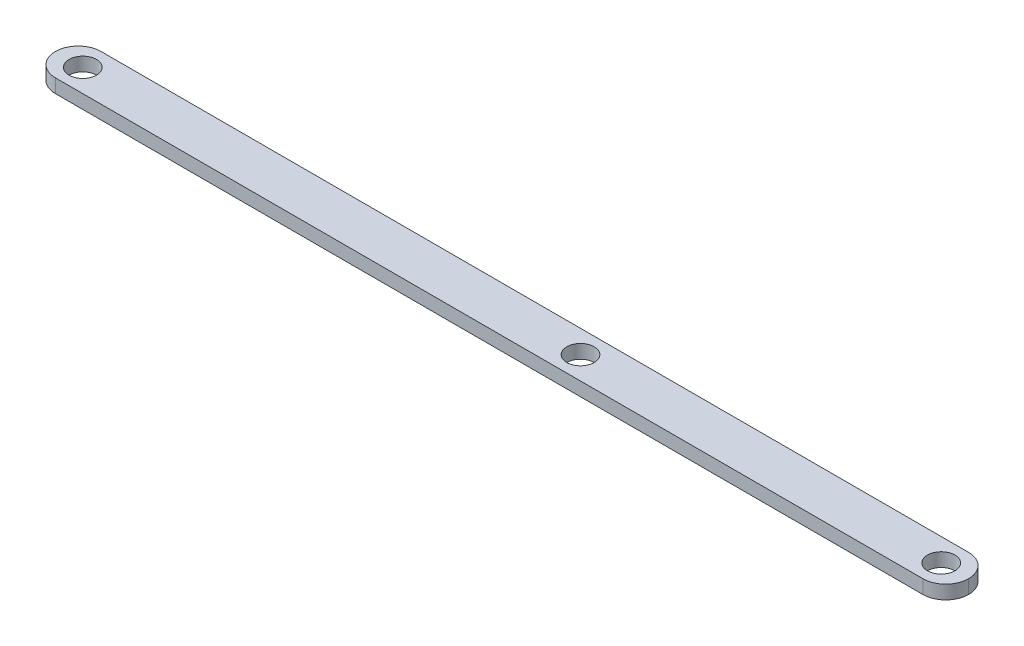
SolidWorks part; units mm, degrees
ref_plane "Front Plane" through (0, 0, 0) normal (0, 0, 1) x (1, 0, 0)
ref_plane "Top Plane" through (0, 0, 0) normal (0, 1, 0) x (1, 0, 0)
ref_plane "Right Plane" through (0, 0, 0) normal (1, 0, 0) x (0, 0, -1)
sketch "Sketch2" plane through (0, 0, 0) normal (0, 1, 0) x (1, 0, 0)
  line L1 (0, 0) -> (200, 0)
  line L2 (0, 0) -> (0, 10)
  line L3 (0, 10) -> (200, 10)
  line L4 (200, 0) -> (200, 10)
  dimension "D1" = 200
  dimension "D2" = 10
extrude "Boss-Extrude1" add sketch "Sketch2" along normal blind 3
sketch "Sketch3" plane through (0, 3, 0) normal (0, 1, 0) x (1, 0, 0)
  line L0 (200, 10) -> (0, 10) construction
  line L1 (0, 10) -> (0, 0) construction
  circle A0 centre (6, 5) radius 3
  dimension "D1" = 5
  dimension "D2" = 6
  dimension "D3" = 6
extrude "Cut-Extrude1" cut sketch "Sketch3" against normal through all
sketch "Sketch4" plane through (0, 3, 0) normal (0, 1, 0) x (1, 0, 0)
  line L0 (200, 10) -> (0, 10) construction
  line L1 (200, 0) -> (200, 10) construction
  circle A0 centre (194, 5) radius 3
  dimension "D1" = 5
  dimension "D3" = 6
  dimension "D2" = 6
extrude "Cut-Extrude2" cut sketch "Sketch4" against normal through all
fillet "Fillet1" radius 5 2 edges at (0, 1.5, -10) (0, 1.5, 0)
fillet "Fillet2" radius 5 2 edges at (200, 1.5, -10) (200, 1.5, 0)
sketch "Sketch5" plane through (0, 3, 0) normal (0, 1, 0) x (1, 0, 0)
  line L0 (5, 0) -> (195, 0) construction
  circle A0 centre (115, 5) radius 3
  point P6 (100, 0)
  dimension "D1" = 115
  dimension "D3" = 6
  dimension "D2" = 5
extrude "Cut-Extrude3" cut sketch "Sketch5" against normal through all
